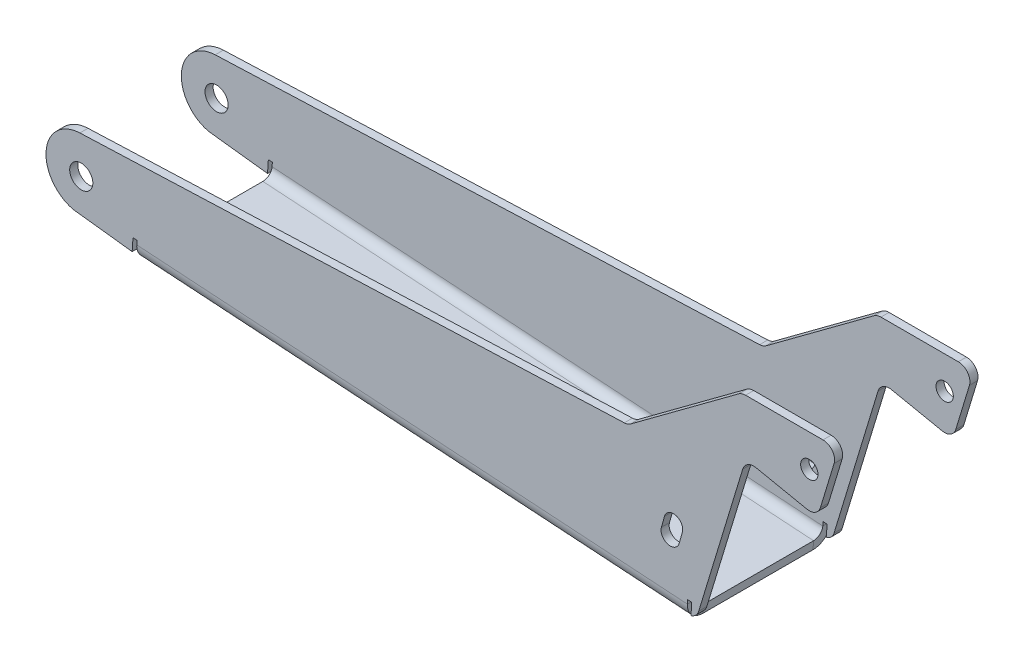
SolidWorks part; units mm, degrees
note: The reader was unsure of these and kept them because the rebuilt part matched: flange length of "Edge-Flange1".
ref_plane "Front Plane" through (0, 0, 0) normal (0, 0, 1) x (1, 0, 0)
ref_plane "Top Plane" through (0, 0, 0) normal (0, 1, 0) x (1, 0, 0)
ref_plane "Right Plane" through (0, 0, 0) normal (1, 0, 0) x (0, 0, -1)
sketch "Sketch1" plane through (0, 0, 0) normal (0, 0, 1) x (1, 0, 0)
  line L0 (170.9232, 175.5757) -> (267.7046, 169.0678) construction
  line L1 (170.9129, 175.4066) -> (266.125, 169.2097)
  line L2 (268.1688, 170.6248) -> (275.7745, 195.6897)
  line L3 (278.0899, 197.0683) -> (286.8931, 195.2639)
  line L4 (289.2085, 196.6424) -> (291.5751, 204.4416)
  line L5 (289.6612, 207.0223) -> (276.2726, 207.0223)
  line L6 (275.0815, 206.629) -> (256.4226, 192.7962)
  line L7 (255.3092, 192.4043) -> (161.1781, 188.7441)
  line L8 (170.9129, 175.4066) -> (160.0193, 176.7108)
  line L9 (263.8006, 181.4562) -> (263.2585, 179.5311) construction
  line L10 (263.8006, 181.4562) -> (263.2585, 179.5311) construction
  line L11 (264.6293, 181.2229) -> (264.0871, 179.2977) construction
  line L12 (262.972, 181.6896) -> (262.4299, 179.7644) construction
  line L13 (263.2585, 179.5311) -> (263.8006, 181.4562) construction
  line L14 (261.7184, 179.9648) -> (262.2606, 181.8899)
  line L15 (264.7986, 179.0974) -> (265.3407, 181.0225)
  arc A0 (161.1781, 188.7441) -> (160.0193, 176.7108) centre (161.4151, 182.6489) ccw
  arc A1 (255.3092, 192.4043) -> (256.4226, 192.7962) centre (255.2315, 194.4028) ccw
  arc A2 (275.0815, 206.629) -> (276.2726, 207.0223) centre (276.2726, 205.0223) cw
  arc A3 (289.6612, 207.0223) -> (291.5751, 204.4416) centre (289.6612, 205.0223) cw
  arc A4 (289.2085, 196.6424) -> (286.8931, 195.2639) centre (287.2947, 197.2232) cw
  arc A5 (278.0899, 197.0683) -> (275.7745, 195.6897) centre (277.6883, 195.109) ccw
  arc A6 (268.1688, 170.6248) -> (266.125, 169.2097) centre (266.2549, 171.2055) cw
  arc A7 (264.6293, 181.2229) -> (262.972, 181.6896) centre (263.8006, 181.4562) ccw construction
  arc A8 (262.4299, 179.7644) -> (264.0871, 179.2977) centre (263.2585, 179.5311) ccw construction
  arc A9 (261.7184, 179.9648) -> (264.7986, 179.0974) centre (263.2585, 179.5311) ccw
  arc A10 (265.3407, 181.0225) -> (262.2606, 181.8899) centre (263.8006, 181.4562) ccw
  circle A11 centre (287.2947, 201.4292) radius 1.5
  circle A12 centre (161.4151, 182.3428) radius 2
  point P26 (267.7081, 169.1067)
  point P27 (263.5296, 180.4936)
  point P32 (263.5296, 180.4936)
  dimension "D2" = 1.6
  dimension "D1" = 97
base flange "Base-Flange1" sketch "Sketch1" thickness 1.4 reverse thickness direction no parameters "D1"=1.5
edge flange "Edge-Flange1" sketch "Sketch8" flange angle 90 flange length 11 flange position material outside bend radius 1.5 thickness 1.4 relief rectangular parameters "D6"=10
sketch "Sketch8" plane through (12.0892, 185.7437, 0) normal (-0.0649, -0.9979, 0) x (0.9979, -0.0649, 0)
  line L2 (159.1598, 0) -> (159.1598, 11)
  line L3 (159.1598, 11) -> (254.5733, 11)
  line L4 (254.5733, 11) -> (254.5733, 0)
  line L7 (159.1598, 0) -> (254.5733, 0) construction
  line L8 (159.1598, 0) -> (254.5733, 0)
bend "EdgeBend1" bend radius 1.5 bend angle 90 parameters "D5"=1
mirror "Mirror1" about plane through (170.822, 174.0096, 11) normal (0, 0, -1) of bodies 102
bend "MirrorBend1" bend radius 1.5 bend angle 90 parameters "D5"=2
ref_plane "Plane1" through (0, 0, 11) normal (0, 0, 1) x (1, 0, 0)
sketch "Bend-Lines1" [suppressed] plane through (0, 0, 0) normal (0, 1, 0) x (1, 0, 0)
sketch "Bounding-Box1" [suppressed] plane through (0, 0, 0) normal (0, 1, 0) x (1, 0, 0)
sheet metal parameters "Sheet-Metal1" thickness 1.4 parameters "D1"=1.5
flat pattern "Flat-Pattern1" [suppressed]
sketch "Bend-Lines2" plane through (0, 0, 0) normal (0, 1, 0) x (1, 0, 0)
sketch3d "Bounding-Box2" [suppressed]
  line L0 (1.3663, -30.3176, 0) -> (-135.1933, -8.6523, 0) construction
  line L1 (6.9803, 5.0687, 0) -> (-129.5793, 26.734, 0) construction
  line L2 (1.3663, -30.3176, 0) -> (6.9803, 5.0687, 0) construction
  line L3 (-135.1933, -8.6523, 0) -> (-129.5793, 26.734, 0) construction
sheet metal parameters "Sheet-Metal2" thickness 1.4 parameters "D1"=1.5
flat pattern "Flat-Pattern1"
sketch "Bend-Lines2" plane through (0, 0, 0) normal (0, 0, 1) x (1, 0, 0)
  line L0 (170.8981, 175.1792) -> (266.1102, 168.9823) construction
  line L1 (170.8981, 175.1792) -> (266.1102, 168.9823) construction
sketch3d "Bounding-Box2" [suppressed]
  line L0 (0.8354, -44.1952, 0) -> (137.395, -22.5299, 0) construction
  line L1 (-6.9803, 5.0687, 0) -> (129.5793, 26.734, 0) construction
  line L2 (0.8354, -44.1952, 0) -> (-6.9803, 5.0687, 0) construction
  line L3 (137.395, -22.5299, 0) -> (129.5793, 26.734, 0) construction
bend of the flat pattern "Flatten-<EdgeBend1>1"
sheet metal parameters "Sheet-Metal3" thickness 1.4 parameters "D1"=1.5
flat pattern "Flat-Pattern3"
sketch "Bend-Lines3" plane through (0, 0, 0) normal (0, 0, 1) x (1, 0, 0)
  line L0 (169.4397, 152.7709) -> (264.6518, 146.574) construction
  line L1 (170.8981, 175.1792) -> (266.1102, 168.9823) construction
  line L2 (169.4397, 152.7709) -> (264.6518, 146.574) construction
  line L3 (170.8981, 175.1792) -> (266.1102, 168.9823) construction
sketch3d "Bounding-Box3" [suppressed]
  line L0 (-3.9659, 32.9827, 0) -> (130.3713, 24.2393, 0) construction
  line L1 (-10.5544, -68.2458, 0) -> (123.7828, -76.9892, 0) construction
  line L2 (-3.9659, 32.9827, 0) -> (-10.5544, -68.2458, 0) construction
  line L3 (130.3713, 24.2393, 0) -> (123.7828, -76.9892, 0) construction
bend of the flat pattern "Flatten-<EdgeBend1>2"
bend of the flat pattern "Flatten-<MirrorBend1>1"
